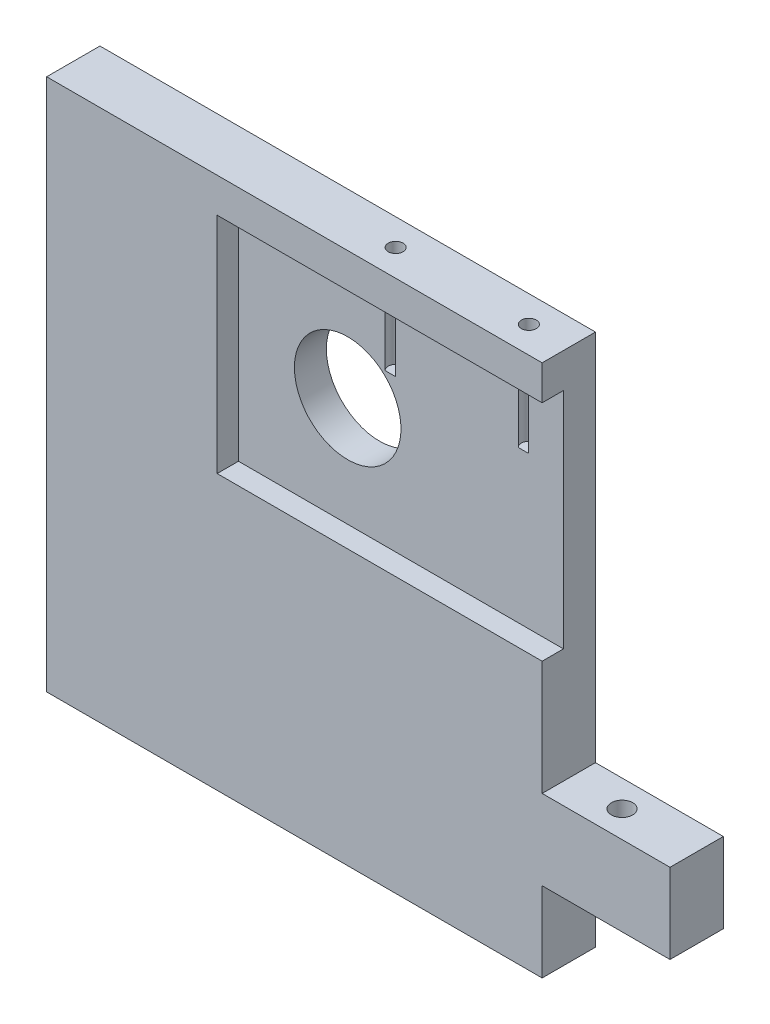
SolidWorks part; units mm, degrees
ref_plane "Front Plane" through (0, 0, 0) normal (0, 0, 1) x (1, 0, 0)
ref_plane "Top Plane" through (0, 0, 0) normal (0, 1, 0) x (1, 0, 0)
ref_plane "Right Plane" through (0, 0, 0) normal (1, 0, 0) x (0, 0, -1)
sketch "Sketch1" plane through (0, 0, 0) normal (0, 0, 1) x (1, 0, 0)
  line L1 (-76.1871, 64.9281) -> (16.8129, 64.9281)
  line L2 (-76.1871, 64.9281) -> (-76.1871, -35.0719)
  line L3 (-76.1871, -35.0719) -> (16.8129, -35.0719)
  line L4 (16.8129, 64.9281) -> (16.8129, -35.0719)
  dimension "D1" = 93
  dimension "D2" = 100
extrude "Boss-Extrude2" add sketch "Sketch1" along normal blind 10 contours L1 L4 L3 L2
sketch "Sketch3" plane through (0, 0, 0) normal (0, 0, -1) x (-1, 0, 0)
  line L0 (76.1871, -35.0719) -> (-16.8129, -35.0719) construction
  line L1 (-16.8129, 64.9281) -> (-6.8129, 64.9281)
  line L2 (-16.8129, 64.9281) -> (-16.8129, -35.0719)
  line L3 (-16.8129, -35.0719) -> (-6.8129, -35.0719)
  line L4 (-6.8129, 64.9281) -> (-6.8129, -35.0719)
  line L5 (-16.8129, 64.9281) -> (-16.8129, -35.0719) construction
  dimension "D1" = 0
  dimension "D2" = 0
  dimension "D3" = 10
  dimension "D4" = 100
extrude "Boss-Extrude3" add sketch "Sketch3" along normal blind 0.01
sketch "Sketch4" plane through (16.8129, 0, 0) normal (1, 0, 0) x (0, 0, -1)
  line L0 (-10, 64.9281) -> (-10, -35.0719) construction
  line L1 (-10, -5.0719) -> (0.01, -5.0719)
  line L2 (-10, -5.0719) -> (-10, -20.0719)
  line L3 (-10, -20.0719) -> (0.01, -20.0719)
  line L4 (0.01, -5.0719) -> (0.01, -20.0719)
  line L5 (0.01, 64.9281) -> (0.01, -35.0719) construction
  line L6 (-10, -35.0719) -> (0.01, -35.0719) construction
  dimension "D1" = 15
  dimension "D2" = 15
extrude "Boss-Extrude4" add sketch "Sketch4" along normal blind 24
sketch "Sketch5" plane through (0, -5.0719, 0) normal (0, 1, 0) x (1, 0, 0)
  line L0 (40.8129, -10) -> (16.8129, -10) construction
  line L2 (16.8129, 0.01) -> (16.8129, -10) construction
  circle A0 centre (26.8129, -5) radius 2
  dimension "D2" = 4
  dimension "D3" = 10
  dimension "D1" = 5
extrude "Cut-Extrude1" cut sketch "Sketch5" against normal blind 50
sketch "Sketch6" plane through (0, 0, -0.01) normal (0, 0, -1) x (-1, 0, 0)
  line L0 (-16.8129, -35.0719) -> (-6.8129, -35.0719) construction
  line L1 (-16.8129, -20.0719) -> (-16.8129, -35.0719) construction
  circle A0 centre (-1.8129, -24.5719) radius 7.5
  dimension "D1" = 15
  dimension "D2" = 10.5
  dimension "D3" = 15
sketch "Sketch7" plane through (0, 0, 0) normal (0, 0, -1) x (-1, 0, 0)
  line L0 (76.1871, -35.0719) -> (-6.8129, -35.0719) construction
  line L2 (-16.8129, 64.9281) -> (-16.8129, -5.0719) construction
  circle A0 centre (23.6871, 36.9281) radius 10
  dimension "D1" = 20
  dimension "D2" = 72
  dimension "D3" = 40.5
extrude "Cut-Extrude3" cut sketch "Sketch7" against normal blind 50
extrude "Extrude-Thin1" add sketch "Sketch7<2>" along normal blind 1 from surface thin starting at face at (-13.6871, 36.9281, 10) thin type one direction reverse wall 2
sketch "Sketch7<2>" plane through (0, 0, 0) normal (0, 0, -1) x (-1, 0, 0) same geometry as "Sketch7"
extrude "Extrude-Thin2" add sketch "Sketch6" along normal blind 1 from surface thin starting at face at (-0.4371, 1.1781, 10) thin type one direction reverse wall 2
sketch "Sketch8" plane through (0, 64.9281, 0) normal (0, 1, 0) x (1, 0, 0)
  line L0 (-76.1871, -10) -> (16.8129, -10) construction
  line L1 (16.8129, 0.01) -> (6.8129, 0.01)
  line L2 (16.8129, 0.01) -> (16.8129, -10)
  line L3 (16.8129, -10) -> (6.8129, -10)
  line L4 (6.8129, 0.01) -> (6.8129, -10)
  line L5 (16.8129, 0.01) -> (6.8129, -10) construction
  line L6 (16.8129, -10) -> (6.8129, 0.01) construction
  line L7 (6.8129, 0.01) -> (6.8129, 0) construction
  circle A0 centre (9.3129, -4.99) radius 1.4
  circle A1 centre (-15.6871, -4.99) radius 1.4
  point P4 (11.8129, -4.995)
  dimension "D1" = 25
  dimension "D3" = 2.8
  dimension "D5" = 5
  dimension "D6" = 5
extrude "Cut-Extrude4" cut sketch "Sketch8" against normal blind 20 contours A1 | A0 region at (-15.6871, 64.9281, 4.99)
sketch "Sketch14" plane through (0, 0, 10) normal (0, 0, 1) x (1, 0, 0)
  line L0 (16.8129, 64.9281) -> (16.8129, -5.0719) construction
  line L1 (-44.1871, 16.4281) -> (16.8129, 16.4281)
  line L2 (-44.1871, 16.4281) -> (-44.1871, 58.4281)
  line L3 (-44.1871, 58.4281) -> (16.8129, 58.4281)
  line L4 (16.8129, 16.4281) -> (16.8129, 58.4281)
  circle A0 centre (-23.6871, 36.9281) radius 8 construction
  dimension "D1" = 42
  dimension "D2" = 20.5
  dimension "D3" = 20.5
extrude "Cut-Extrude8" cut sketch "Sketch14" against normal blind 4
sketch "Sketch15" plane through (0, 0, 0) normal (0, 0, -1) x (-1, 0, 0)
  circle A0 centre (23.6871, 36.9281) radius 10
  circle A1 centre (23.6871, 36.9281) radius 10 construction
  dimension "D1" = 20
  dimension "D2" = 0
